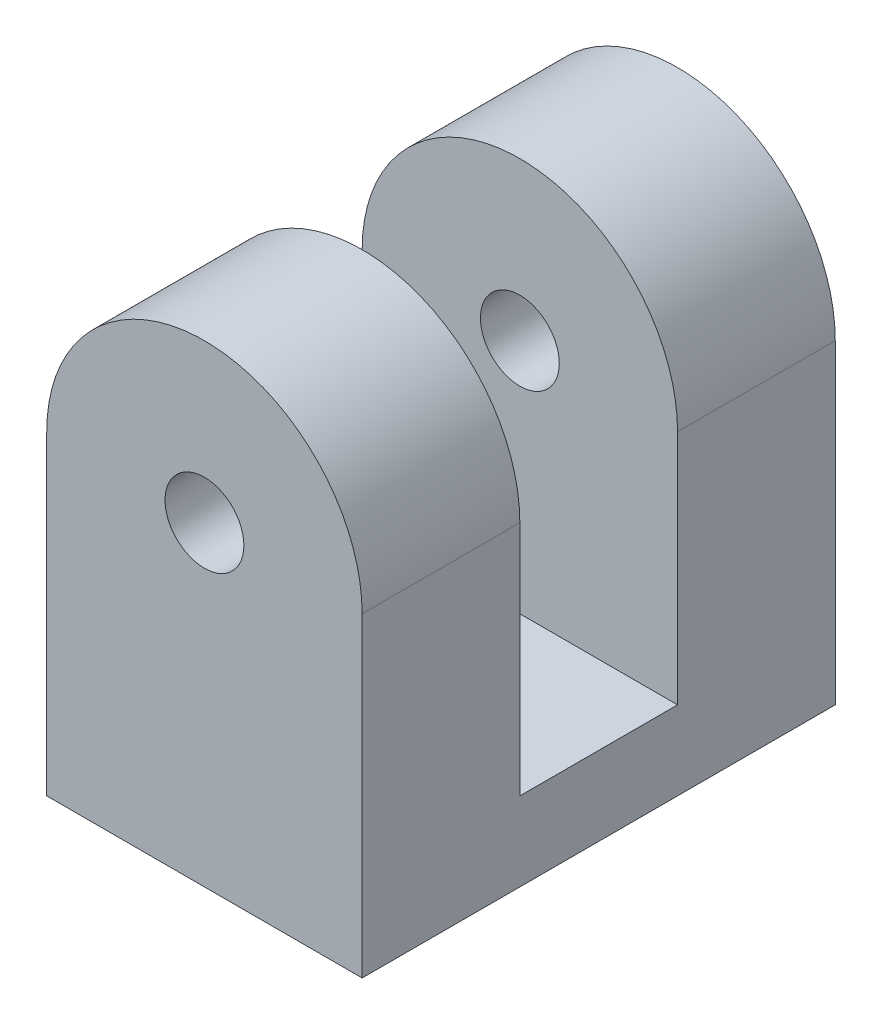
SolidWorks part; units mm, degrees
ref_plane "Front" through (0, 0, 0) normal (0, 0, 1) x (1, 0, 0)
ref_plane "Top" through (0, 0, 0) normal (0, 1, 0) x (1, 0, 0)
ref_plane "Right" through (0, 0, 0) normal (1, 0, 0) x (0, 0, -1)
sketch "Sketch1" plane through (0, 0, 0) normal (0, 0, 1) x (1, 0, 0)
  line L0 (0, -55) -> (0, 55) construction
  line L2 (-10, 15) -> (-10, 0)
  line L3 (-10, 0) -> (10, 0)
  line L4 (10, 15) -> (10, 0)
  line L5 (55, 0) -> (-55, 0) construction
  arc A0 (-10, 15) -> (10, 15) centre (0, 15) cw
  circle A1 centre (0, 15) radius 2.5
  point P0 (0, 0)
  dimension "D1" = 5
  dimension "D2" = 20
  dimension "D3" = 15
extrude "Boss-Extrude1" add sketch "Sketch1" along normal blind 10 from offset 5
extrude "Boss-Extrude2" add sketch "Sketch1<2>" against normal blind 10 from offset 5 separate body offset against normal yes
sketch "Sketch1<2>" plane through (0, 0, 0) normal (0, 0, 1) x (1, 0, 0) same geometry as "Sketch1"
sketch "Sketch2" plane through (0, 0, 0) normal (0, -1, 0) x (1, 0, 0)
  line L0 (10, -15) -> (10, -5) construction
  line L1 (-10, 15) -> (10, 15)
  line L2 (-10, 15) -> (-10, -15)
  line L3 (-10, -15) -> (10, -15)
  line L4 (10, 15) -> (10, -15)
  line L5 (-10, 15) -> (10, -15) construction
  line L6 (-10, -15) -> (10, 15) construction
  point P0 (0, 0)
extrude "Boss-Extrude3" add sketch "Sketch2" along normal blind 5
